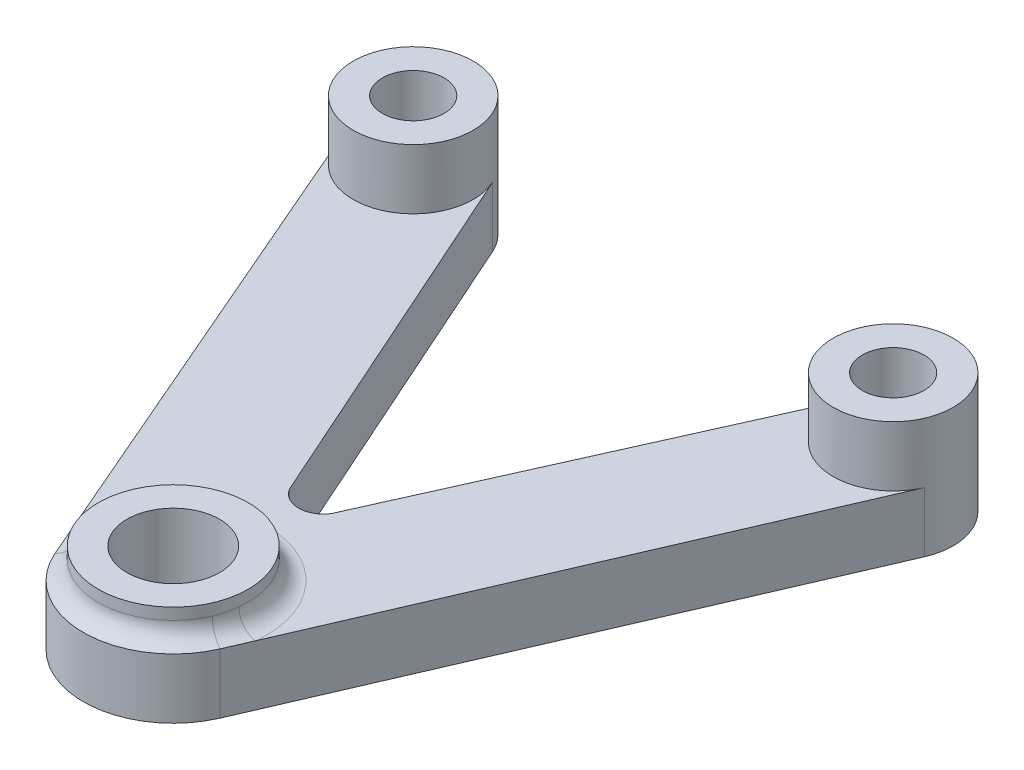
SolidWorks part; units mm, degrees
ref_plane "Front Plane" through (0, 0, 0) normal (0, 0, 1) x (1, 0, 0)
ref_plane "Top Plane" through (0, 0, 0) normal (0, 1, 0) x (1, 0, 0)
ref_plane "Right Plane" through (0, 0, 0) normal (1, 0, 0) x (0, 0, -1)
sketch "Sketch1" plane through (0, 0, 0) normal (0, 1, 0) x (1, 0, 0)
  line L0 (0, 3.2576) -> (0, 54.0576) construction
  line L1 (25.4, 54.0576) -> (-25.4, 54.0576) construction
  line L2 (-2.2602, 17.8405) -> (-19.6025, 56.6484)
  line L3 (2.2602, 17.8405) -> (19.6025, 56.6484)
  line L4 (-1.9098, 19.1326) -> (1.9098, 19.1326) construction
  line L5 (-31.2295, 51.5398) -> (-8.7442, -0.5192)
  line L6 (31.2295, 51.5398) -> (8.7442, -0.5192)
  circle A0 centre (0, 3.2576) radius 4.7625 construction
  circle A1 centre (-25.4, 54.0576) radius 2.3813 construction
  circle A2 centre (25.4, 54.0576) radius 2.3812 construction
  arc A3 (-19.6025, 56.6484) -> (-31.2295, 51.5398) centre (-25.4, 54.0576) ccw
  arc A4 (19.6025, 56.6484) -> (31.2295, 51.5398) centre (25.4, 54.0576) cw
  arc A5 (-8.7442, -0.5192) -> (8.7442, -0.5192) centre (0, 3.2576) ccw
  arc A6 (-2.2602, 17.8405) -> (2.3448, 18.0012) centre (0, 19.1326) ccw
  circle A7 centre (0, 3.2576) radius 7.9375
  point P7 (0, 54.0576)
  point P17 (0, 19.1326)
  dimension "D1" = 50.8
  dimension "D3" = 9.525
  dimension "D4" = 12.7
  dimension "D5" = 15.875
  dimension "D6" = 19.05
  dimension "D2" = 50.8
extrude "Boss-Extrude1" add sketch "Sketch1" along normal blind 6.35 contours A6 L2 A3 L5 A5 L6 A4 L3 region at (0, 0, -15.6084)
hole_wizard "F (0.257) Diameter Hole1" positions "Sketch3" profile "Sketch2" hole size "F" standard "ANSI Inch" end condition through all
sketch "Sketch3" plane through (0, 6.35, 0) normal (0, 1, 0) x (1, 0, 0)
  line L0 (-27.9544, 59.8712) -> (-25.4, 54.0576) construction
  line L1 (27.9544, 59.8712) -> (25.4, 54.0576) construction
  arc A0 (-19.6025, 56.6484) -> (-31.2295, 51.5398) centre (-25.4, 54.0576) ccw construction
  arc A1 (31.2295, 51.5398) -> (19.6025, 56.6484) centre (25.4, 54.0576) ccw construction
  point P3 (-25.4, 54.0576)
  point P13 (25.4, 54.0576)
sketch "Sketch2" plane through (-25.4, 6.35, -54.0576) normal (1, 0, 0) x (0, 0, 1)
  line L0 (0, 0) -> (0, 6.35)
  line L1 (0, 6.35) -> (3.2639, 6.35)
  line L2 (3.2639, 6.35) -> (3.2639, 0)
  line L5 (3.2639, 0) -> (0, 0)
  line L11 (0, -6.35) -> (0, 107.95) construction
  dimension "Thru Hole Dia." = 6.5278
  dimension "Thru Hole Depth" = 6.35
extrude "Boss-Extrude2" add sketch "Sketch1<3>" along normal blind 9.525 contours A7 region at (0, 0, -3.2576)
sketch "Sketch1<3>" plane through (0, 0, 0) normal (0, 1, 0) x (1, 0, 0) same geometry as "Sketch1"
hole_wizard "W (0.386) Diameter Hole1" positions "Sketch8" profile "Sketch7" hole size "W" standard "ANSI Inch" end condition up to next
sketch "Sketch8" plane through (0, 9.525, 0) normal (0, 1, 0) x (1, 0, 0)
  line L0 (0, -4.6799) -> (0, 11.1951) construction
  circle A0 centre (0, 3.2576) radius 7.9375 construction
  point P7 (0, 3.2576)
sketch "Sketch7" plane through (0, 9.525, -3.2576) normal (1, 0, 0) x (0, 0, 1)
  line L0 (0, 0) -> (0, 9.525)
  line L1 (0, 9.525) -> (4.9022, 9.525)
  line L2 (4.9022, 9.525) -> (4.9022, 0)
  line L5 (4.9022, 0) -> (0, 0)
  line L11 (0, -6.35) -> (0, 107.95) construction
  dimension "Thru Hole Dia." = 9.8044
  dimension "Thru Hole Depth" = 9.525
fillet "Fillet1" radius 2 1 edges at (0, 6.35, 4.6799)
hole_wizard "25/64 (0.39063) Diameter Hole1" positions "Sketch10" profile "Sketch11" hole size "25/64" standard "ANSI Inch"
sketch "Sketch10" plane through (0, 6.35, 0) normal (0, 1, 0) x (1, 0, 0)
  point P0 (-25.4, 54.0576)
  point P3 (25.4, 54.0576)
sketch "Sketch11" plane through (-25.4, 6.35, -54.0576) normal (1, 0, 0) x (0, 0, 1)
  line L0 (0, 0) -> (0, 1.524)
  line L1 (0, 1.524) -> (4.961, 1.524)
  line L2 (4.961, 1.524) -> (4.961, 0)
  line L5 (4.961, 0) -> (0, 0)
  line L10 (0, 1.524) -> (-4.961, 1.524) construction
  line L11 (0, -6.35) -> (0, 107.95) construction
  dimension "Hole Dia." = 9.922
  dimension "Hole Depth" = 1.524
  dimension "Drill Angle" = 180
sketch "Sketch12" plane through (0, 6.35, 0) normal (0, 1, 0) x (1, 0, 0)
  circle A0 centre (25.4, 54.0576) radius 6.35
  circle A1 centre (-25.4, 54.0576) radius 6.35
  circle A2 centre (25.4, 54.0576) radius 3.2639
  circle A3 centre (-25.4, 54.0576) radius 3.2639
extrude "Boss-Extrude3" add sketch "Sketch12" along normal blind 6.35 and the other way blind 2.54
